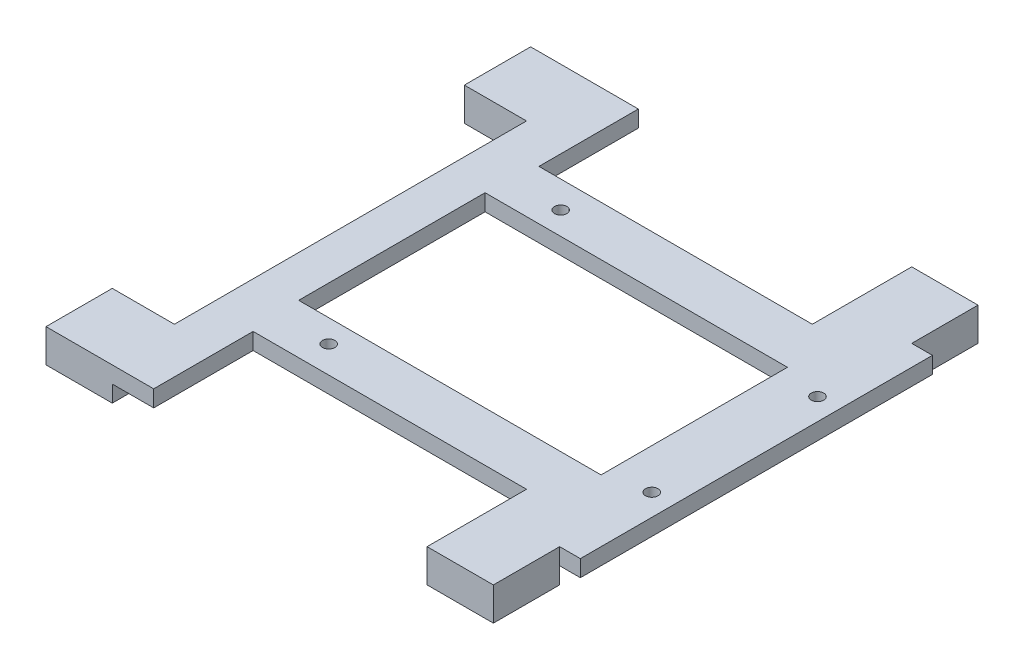
SolidWorks part; units mm, degrees
ref_plane "Front Plane" through (0, 0, 0) normal (0, 0, 1) x (1, 0, 0)
ref_plane "Top Plane" through (0, 0, 0) normal (0, 1, 0) x (1, 0, 0)
ref_plane "Right Plane" through (0, 0, 0) normal (1, 0, 0) x (0, 0, -1)
sketch "Sketch1" plane through (0, 0, 0) normal (0, 1, 0) x (1, 0, 0)
  line L1 (-56.5, 42.5) -> (56.5, 42.5)
  line L2 (-56.5, 42.5) -> (-56.5, -42.5)
  line L3 (-56.5, -42.5) -> (56.5, -42.5)
  line L4 (56.5, 42.5) -> (56.5, -42.5)
  line L5 (-56.5, 42.5) -> (56.5, -42.5) construction
  line L6 (-56.5, -42.5) -> (56.5, 42.5) construction
  point P0 (0, 0)
  dimension "D1" = 113
  dimension "D2" = 85
extrude "Boss-Extrude1" add sketch "Sketch1" along normal blind 4
sketch "Sketch2" plane through (0, 4, 0) normal (0, 1, 0) x (1, 0, 0)
  line L0 (0, 42.5) -> (0, -42.5) construction
  line L1 (56.5, 42.5) -> (-56.5, 42.5) construction
  line L2 (-56.5, -42.5) -> (56.5, -42.5) construction
  line L4 (-56.5, 0) -> (56.5, 0) construction
  line L5 (-56.5, 42.5) -> (-56.5, -42.5) construction
  line L6 (56.5, -42.5) -> (56.5, 42.5) construction
  circle A46 centre (-18.75, 28) radius 1.5
  circle A47 centre (-18.75, -28) radius 1.5
  circle A48 centre (51.25, -20) radius 1.5
  circle A49 centre (51.25, 20) radius 1.5
  line B0 (-25.4814, 0) -> (70.4814, 0) construction
  arc B1 (-19.5394, -30.8943) -> (-19.2077, -30.9649) centre (-18.75, -28) ccw construction
  arc B2 (-21.6443, -28.7894) -> (-19.5394, -30.8943) centre (-18.75, -28) ccw construction
  arc B3 (-21.7149, -28.4577) -> (-21.6443, -28.7894) centre (-18.75, -28) ccw construction
  arc B4 (-19.2077, 30.9649) -> (-19.5394, 30.8943) centre (-18.75, 28) ccw construction
  arc B5 (-19.5394, 30.8943) -> (-21.6443, 28.7894) centre (-18.75, 28) ccw construction
  arc B6 (-21.6443, 28.7894) -> (-21.7149, 28.4577) centre (-18.75, 28) ccw construction
  arc B7 (-21.7149, 28.4577) -> (-21.7149, -28.4577) centre (83.9083, 0) ccw construction
  arc B8 (-19.2077, -30.9649) -> (9.25, -34.7314) centre (9.25, 74.6583) ccw construction
  arc B9 (9.25, -34.7314) -> (63.3655, -15.1715) centre (9.25, 49.9083) ccw construction
  arc B10 (63.3655, -15.1715) -> (63.3655, 15.1715) centre (50.75, 0) ccw construction
  arc B11 (63.3655, 15.1715) -> (9.25, 34.7314) centre (9.25, -49.9083) ccw construction
  arc B12 (9.25, 34.7314) -> (-19.2077, 30.9649) centre (9.25, -74.6583) ccw construction
  arc B13 (51.25, 22.5132) -> (51.25, 17.4868) centre (51.25, 20) ccw construction
  arc B14 (51.25, 17.5) -> (51.25, 22.5) centre (51.25, 20) ccw construction
  arc B15 (51.25, -17.5) -> (51.25, -22.5) centre (51.25, -20) ccw construction
  arc B16 (51.25, -22.5132) -> (51.25, -17.4868) centre (51.25, -20) ccw construction
  arc B17 (-18.75, -25.5) -> (-18.75, -30.5) centre (-18.75, -28) ccw construction
  arc B18 (-18.75, -30.5132) -> (-18.75, -25.4868) centre (-18.75, -28) ccw construction
  arc B19 (-18.75, 30.5) -> (-18.75, 25.5) centre (-18.75, 28) ccw construction
  arc B20 (-18.75, 25.5) -> (-18.75, 30.5) centre (-18.75, 28) ccw construction
  dimension "D1" = 3
  dimension "D2" = 3
  dimension "D3" = 3
  dimension "D4" = 3
  dimension "D5" = 34
sketch_block_instance "Block2-1"
sketch_block "Block2"
extrude "Cut-Extrude1" cut sketch "Sketch2" against normal through all contours A46 | A49 | A47 | A48
sketch "Sketch4" plane through (0, 0, 0) normal (0, -1, 0) x (1, 0, 0)
  line L0 (-56.5, 42.5) -> (56.5, 42.5) construction
  line L5 (-56.5, 42.5) -> (-40.5, 42.5)
  line L6 (-56.5, 42.5) -> (-56.5, 58.5)
  line L7 (-56.5, 58.5) -> (-40.5, 58.5)
  line L8 (-40.5, 42.5) -> (-40.5, 58.5)
  line L9 (51.5, 42.5) -> (35.5, 42.5)
  line L10 (51.5, 42.5) -> (51.5, 58.5)
  line L11 (51.5, 58.5) -> (35.5, 58.5)
  line L12 (35.5, 42.5) -> (35.5, 58.5)
  line L18 (56.5, 42.5) -> (56.5, -42.5) construction
  line L19 (0, 0) -> (-56.5, 0) construction
  line L20 (-56.5, -42.5) -> (-56.5, 42.5) construction
  line L21 (51.5, -58.5) -> (35.5, -58.5)
  line L22 (35.5, -42.5) -> (35.5, -58.5)
  line L23 (51.5, -42.5) -> (35.5, -42.5)
  line L24 (51.5, -42.5) -> (51.5, -58.5)
  line L25 (-56.5, -58.5) -> (-40.5, -58.5)
  line L26 (-40.5, -42.5) -> (-40.5, -58.5)
  line L27 (-56.5, -42.5) -> (-40.5, -42.5)
  line L28 (-56.5, -42.5) -> (-56.5, -58.5)
  dimension "D1" = 16
  dimension "D2" = 16
  dimension "D3" = 5
  dimension "D4" = 16
  dimension "D5" = 16
extrude "Boss-Extrude3" add sketch "Sketch4" against normal up to surface (4 mm away) and the other way blind 1 up to face at (-18.75, 4, -26.5)
sketch "Sketch10" plane through (0, 4, 0) normal (0, 1, 0) x (1, 0, 0)
  line L0 (-40.5, -58.5) -> (-56.5, -58.5) construction
  line L1 (-40.5, -42.5) -> (-30.5, -42.5)
  line L2 (-40.5, -42.5) -> (-40.5, -58.5)
  line L3 (-40.5, -58.5) -> (-30.5, -58.5)
  line L4 (-30.5, -42.5) -> (-30.5, -58.5)
  line L5 (-40.5, 42.5) -> (-30.5, 42.5)
  line L6 (-40.5, 42.5) -> (-40.5, 58.5)
  line L7 (-40.5, 58.5) -> (-30.5, 58.5)
  line L8 (-30.5, 42.5) -> (-30.5, 58.5)
  line L9 (-56.5, 58.5) -> (-40.5, 58.5) construction
  dimension "D1" = 10
  dimension "D2" = 10
extrude "Boss-Extrude6" add sketch "Sketch10" against normal up to surface (4 mm away) up to face at (-18.75, 0, -26.5)
sketch "Sketch6" plane through (0, 4, 0) normal (0, 1, 0) x (1, 0, 0)
  line L0 (35.5, 42.5) -> (35.5, 58.5) construction
  line L1 (-31.5, 22.5) -> (41.5, 22.5)
  line L2 (-31.5, 22.5) -> (-31.5, -22.5)
  line L3 (-31.5, -22.5) -> (41.5, -22.5)
  line L4 (41.5, 22.5) -> (41.5, -22.5)
  line L5 (35.5, -58.5) -> (35.5, -42.5) construction
  line L6 (35.5, 42.5) -> (-30.5, 42.5) construction
  line L7 (-30.5, -42.5) -> (35.5, -42.5) construction
  line L8 (-56.5, 58.5) -> (-56.5, -58.5) construction
  line L9 (-41.5, 0) -> (-56.5, 0) construction
  line L10 (-56.5, 42.5) -> (-41.5, 42.5)
  line L11 (-56.5, 42.5) -> (-56.5, -42.5)
  line L12 (-56.5, -42.5) -> (-41.5, -42.5)
  line L13 (-41.5, 42.5) -> (-41.5, -42.5)
  line L14 (-31.5, 0) -> (41.5, 0) construction
  line L15 (-30.5, 42.5) -> (35.5, 42.5)
  line L16 (-30.5, 42.5) -> (-30.5, 34.5)
  line L17 (-30.5, 34.5) -> (35.5, 34.5)
  line L18 (35.5, 42.5) -> (35.5, 34.5)
  line L19 (-30.5, -42.5) -> (35.5, -42.5)
  line L20 (-30.5, -42.5) -> (-30.5, -34.5)
  line L21 (-30.5, -34.5) -> (35.5, -34.5)
  line L22 (35.5, -42.5) -> (35.5, -34.5)
  line L23 (56.5, -42.5) -> (56.5, 42.5) construction
  dimension "D1" = 20
  dimension "D2" = 20
  dimension "D3" = 25
  dimension "D4" = 15
  dimension "D5" = 85
  dimension "D6" = 8
  dimension "D7" = 8
  dimension "D8" = 15
extrude "Cut-Extrude2" cut sketch "Sketch6" against normal through all
sketch "Sketch8" plane through (0, -1, 0) normal (0, -1, 0) x (1, 0, 0)
  line L0 (-56.5, 58.5) -> (-40.5, 58.5) construction
  line L1 (-56.5, 58.5) -> (-56.5, 42.5) construction
  line L2 (-56.5, 42.5) -> (-40.5, 42.5) construction
  line L3 (-40.5, 58.5) -> (-40.5, 42.5) construction
  line L4 (35.5, 58.5) -> (51.5, 58.5) construction
  line L5 (35.5, 58.5) -> (35.5, 42.5) construction
  line L6 (35.5, 42.5) -> (51.5, 42.5) construction
  line L7 (51.5, 58.5) -> (51.5, 42.5) construction
  line L8 (-56.5, 58.5) -> (-40.5, 42.5) construction
  line L9 (-56.5, 42.5) -> (-40.5, 58.5) construction
  line L10 (35.5, 58.5) -> (51.5, 42.5) construction
  line L11 (35.5, 42.5) -> (51.5, 58.5) construction
  line L12 (51.5, 58.5) -> (35.5, 58.5) construction
  line L13 (0, 0) -> (-56.5, 0) construction
  line L14 (-56.5, 42.5) -> (-40.5, 42.5) construction
  line L15 (35.5, 42.5) -> (51.5, 42.5) construction
  circle A0 centre (-48.5, 50.5) radius 6.1
  circle A1 centre (43.5, 50.5) radius 6.1
  circle A2 centre (43.5, -50.5) radius 6.1
  circle A3 centre (-48.5, -50.5) radius 6.1
  dimension "D3" = 12.2
  dimension "D4" = 12.2
extrude "Cut-Extrude3" cut sketch "Sketch8" against normal blind 3.2
sketch "Sketch9" plane through (0, -1, 0) normal (0, -1, 0) x (1, 0, 0)
  line L0 (-55.5, 57.5) -> (-55.5, 43.5)
  line L1 (-56.5, 58.5) -> (-40.5, 58.5)
  line L2 (-56.5, 58.5) -> (-56.5, 42.5)
  line L3 (-56.5, 42.5) -> (-40.5, 42.5)
  line L4 (-40.5, 58.5) -> (-40.5, 42.5)
  line L5 (35.5, 58.5) -> (51.5, 58.5)
  line L6 (35.5, 58.5) -> (35.5, 42.5)
  line L7 (35.5, 42.5) -> (51.5, 42.5)
  line L8 (51.5, 58.5) -> (51.5, 42.5)
  line L9 (-55.5, 43.5) -> (-41.5, 43.5)
  line L10 (-41.5, 57.5) -> (-41.5, 43.5)
  line L11 (-55.5, 57.5) -> (-41.5, 57.5)
  line L16 (0, 0) -> (-56.5, 0) construction
  line L17 (36.5, -43.5) -> (50.5, -43.5)
  line L18 (36.5, -57.5) -> (36.5, -43.5)
  line L19 (50.5, -57.5) -> (36.5, -57.5)
  line L20 (50.5, 43.5) -> (50.5, 57.5)
  line L21 (50.5, 57.5) -> (36.5, 57.5)
  line L22 (36.5, 57.5) -> (36.5, 43.5)
  line L23 (36.5, 43.5) -> (50.5, 43.5)
  line L24 (50.5, 43.5) -> (50.5, 57.5)
  line L25 (50.5, 57.5) -> (36.5, 57.5)
  line L26 (36.5, 57.5) -> (36.5, 43.5)
  line L27 (36.5, 43.5) -> (50.5, 43.5)
  line L28 (50.5, -43.5) -> (50.5, -57.5)
  line L29 (-55.5, -57.5) -> (-41.5, -57.5)
  line L30 (-41.5, -57.5) -> (-41.5, -43.5)
  line L31 (-55.5, -43.5) -> (-41.5, -43.5)
  line L32 (51.5, -58.5) -> (51.5, -42.5)
  line L33 (35.5, -42.5) -> (51.5, -42.5)
  line L34 (35.5, -58.5) -> (35.5, -42.5)
  line L35 (35.5, -58.5) -> (51.5, -58.5)
  line L36 (-40.5, -58.5) -> (-40.5, -42.5)
  line L37 (-56.5, -42.5) -> (-40.5, -42.5)
  line L38 (-56.5, -58.5) -> (-56.5, -42.5)
  line L39 (-56.5, -58.5) -> (-40.5, -58.5)
  line L40 (-55.5, -57.5) -> (-55.5, -43.5)
  dimension "D1" = 1
  dimension "D2" = 1
extrude "Boss-Extrude5" add sketch "Sketch9" along normal blind 3
fillet "Fillet1" radius 0.2 4 edges at (43.5, -1, -44.4) (-48.5, -1, -44.4) (43.5, -1, 44.4) (-48.5, -1, 44.4)
